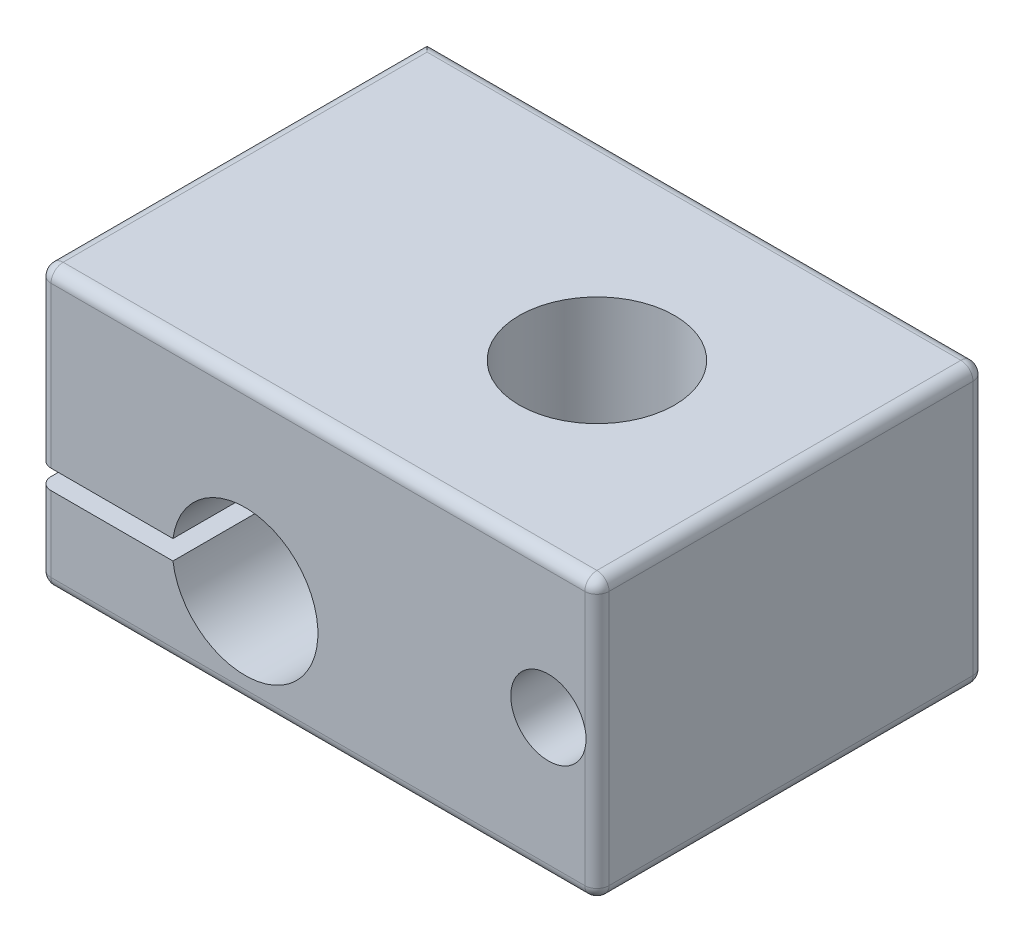
SolidWorks part; units mm, degrees
material "Alloy Steel"
ref_plane "Front Plane" through (0, 0, 0) normal (0, 0, 1) x (1, 0, 0)
ref_plane "Top Plane" through (0, 0, 0) normal (0, 1, 0) x (1, 0, 0)
ref_plane "Right Plane" through (0, 0, 0) normal (1, 0, 0) x (0, 0, -1)
sketch "Sketch1" plane through (0, 0, 0) normal (0, 1, 0) x (1, 0, 0)
  line L1 (11.5, -8) -> (-11.5, -8)
  line L2 (11.5, -8) -> (11.5, 8)
  line L3 (11.5, 8) -> (-11.5, 8)
  line L4 (-11.5, -8) -> (-11.5, 8)
  line L5 (0, 8) -> (0, -8) construction
  line L6 (11.5, 0) -> (-11.5, 0) construction
  point P0 (0, 0)
  dimension "D1" = 16
  dimension "D2" = 23
extrude "Boss-Extrude1" add sketch "Sketch1" along normal blind 11.5
sketch "Sketch2" plane through (0, 0, 8) normal (0, 0, 1) x (1, 0, 0)
  line L0 (-11.5, 0) -> (11.5, 0) construction
  line L1 (-5.9732, 4.4) -> (-11.5, 4.4)
  line L2 (-11.5, 11.5) -> (-11.5, 0) construction
  line L3 (-11.5, 4.4) -> (-11.5, 3.6)
  line L4 (-11.5, 3.6) -> (-5.9732, 3.6)
  line L5 (-11.5, 4) -> (-3, 4) construction
  line L6 (11.5, 11.5) -> (11.5, 0) construction
  arc A0 (-5.9732, 3.6) -> (-5.9732, 4.4) centre (-3, 4) ccw
  circle A1 centre (9.5, 5.75) radius 1.55
  dimension "D1" = 6
  dimension "D5" = 3.1
  dimension "D2" = 4
  dimension "D3" = 14.5
  dimension "D4" = 0.8
  dimension "D6" = 2
  dimension "D7" = 5.75
extrude "Cut-Extrude1" cut sketch "Sketch2" against normal through all
sketch "Sketch3" plane through (0, 0, 0) normal (0, -1, 0) x (1, 0, 0)
  line L0 (11.5, 8) -> (11.5, -8) construction
  line L1 (-11.5, 8) -> (11.5, 8) construction
  line L2 (11.5, -8) -> (-11.5, -8) construction
  circle A0 centre (3.5, 0) radius 3
  circle A1 centre (-9, 0) radius 1.5
  dimension "D1" = 8
  dimension "D3" = 6
  dimension "D4" = 20.5
  dimension "D5" = 3
  dimension "D2" = 8
  dimension "D6" = 8
fillet "Fillet1" radius 0.5 13 edges at (-11.5, 1.8, 8) (-11.5, 7.95, 8) (11.5, 5.75, -8) (-11.5, 1.8, -8) (11.5, 5.75, 8) (11.5, 0, 0) (0, 0, -8) (-11.5, 0, 0) (0, 0, 8) (0, 11.5, -8) (11.5, 11.5, 0) (-11.5, 11.5, 0) (0, 11.5, 8)
hole_wizard "M6 Clearance Hole1" positions "Sketch4" profile "Sketch5" hole size "M6" standard "ANSI Metric" end condition through all
sketch "Sketch4" plane through (0, 0, 0) normal (0, -1, 0) x (-1, 0, 0)
  point P0 (-3.5, 0)
sketch "Sketch5" plane through (3.5, 0, 0) normal (1, 0, 0) x (0, 0, -1)
  line L0 (0, 0) -> (0, 11.5)
  line L1 (0, 11.5) -> (3.2, 11.5)
  line L2 (3.2, 11.5) -> (3.2, 0)
  line L5 (3.2, 0) -> (0, 0)
  line L11 (0, -6.35) -> (0, 107.95) construction
  dimension "Thru Hole Dia." = 6.4
  dimension "Thru Hole Depth" = 11.5
thread "Thread1" [suppressed] pitch 1 start angle 0, offset 0, length 0, pitch 1, diameter 5
ref_plane "Plane1" through (6, 0, 0) normal (0, 0, 1) x (1, 0, 0)
sketch "Thread Profile1" plane through (6, 0, 0) normal (0, 0, 1) x (1, 0, 0)
  line L0 (0, 0) -> (0, 1) construction
  line L1 (0, 0) -> (0.5413, 0.3125)
  line L2 (0.5413, 0.3125) -> (0.5413, 0.4375)
  line L3 (0.5413, 0.4375) -> (0, 0.75)
  line L4 (0.5413, 0.375) -> (0, 0.375) construction
  line L11 (0, 0) -> (0, 0.75)
  point P2 (0, 0)
  dimension "Pitch" = 1
  dimension "Profile_Angle" = 60
  dimension "Profile_Land" = 0.125
  dimension "Profile_Height" = 0.5413
hole_wizard "Tap Drill for M3x0.5 Tap1" positions "Sketch9" profile "Sketch10" hole size "M3x0.5" standard "ANSI Metric"
sketch "Sketch9" plane through (0, 0, 0) normal (0, -1, 0) x (-1, 0, 0)
  point P0 (9, 0)
sketch "Sketch10" plane through (-9, 0, 0) normal (1, 0, 0) x (0, 0, -1)
  line L0 (0, 0) -> (0, 5.1501)
  line L1 (0, 5.1501) -> (1.25, 4.399)
  line L2 (1.25, 4.399) -> (1.25, 0)
  line L5 (1.25, 0) -> (0, 0)
  line L10 (0, 5.1501) -> (-1.25, 4.399) construction
  line L11 (0, -6.35) -> (0, 107.95) construction
  dimension "Hole Dia." = 2.5
  dimension "Hole Depth" = 4.399
  dimension "Drill Angle" = 118
thread "Thread2" [suppressed] pitch 0.5 start angle 0, offset 0, length 0, pitch 0.5, diameter 2.5
ref_plane "Plane2" through (-7.75, 0, 0) normal (0, 0, 1) x (1, 0, 0)
sketch "Thread Profile2" plane through (-7.75, 0, 0) normal (0, 0, 1) x (1, 0, 0)
  line L0 (0, 0) -> (0, 0.5) construction
  line L1 (0, 0) -> (0.2706, 0.1562)
  line L2 (0.2706, 0.1562) -> (0.2706, 0.2187)
  line L3 (0.2706, 0.2187) -> (0, 0.375)
  line L4 (0.2706, 0.1875) -> (0, 0.1875) construction
  line L11 (0, 0) -> (0, 0.375)
  point P2 (0, 0)
  dimension "Pitch" = 0.5
  dimension "Profile_Angle" = 60
  dimension "Profile_Land" = 0.0625
  dimension "Profile_Height" = 0.2706
